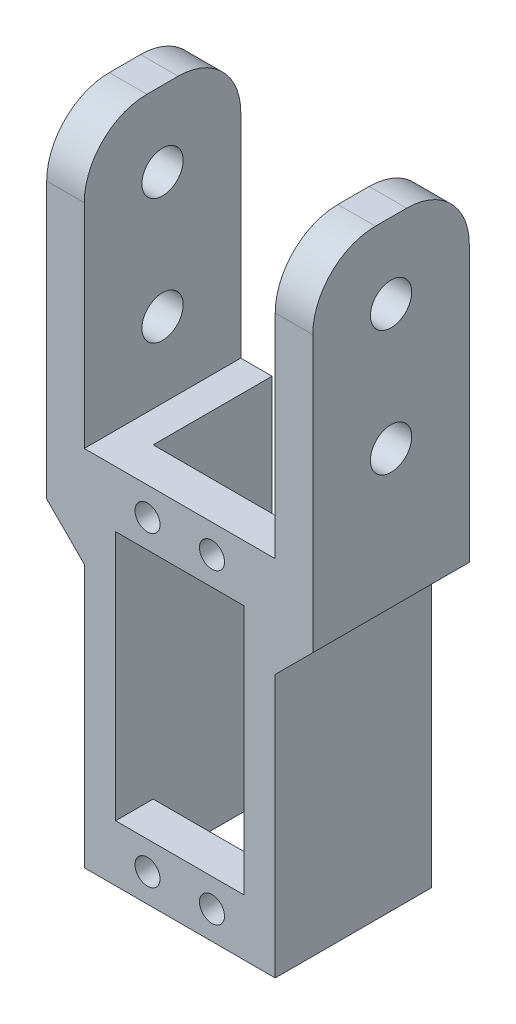
SolidWorks part; units mm, degrees
ref_plane "Front Plane" through (0, 0, 0) normal (0, 0, 1) x (1, 0, 0)
ref_plane "Top Plane" through (0, 0, 0) normal (0, 1, 0) x (1, 0, 0)
ref_plane "Right Plane" through (0, 0, 0) normal (1, 0, 0) x (0, 0, -1)
sketch "Sketch1" plane through (0, 0, 0) normal (0, 0, 1) x (1, 0, 0)
  line L1 (0, 0) -> (20.5, 0)
  line L2 (0, 0) -> (0, 9)
  line L3 (0, 9) -> (20.5, 9)
  line L4 (20.5, 0) -> (20.5, 9)
  dimension "D1" = 20.5
  dimension "D2" = 9
extrude "Boss-Extrude1" add sketch "Sketch1" along normal blind 6
sketch "Sketch2" plane through (20.5, 0, 0) normal (1, 0, 0) x (0, 0, -1)
  line L1 (-6, 9) -> (19, 9)
  line L2 (-6, 9) -> (-6, -49)
  line L3 (-6, -49) -> (19, -49)
  line L4 (19, 9) -> (19, -49)
  dimension "D1" = 25
  dimension "D2" = 58
extrude "Boss-Extrude2" add sketch "Sketch2" along normal blind 5
pattern_linear "LPattern1" count 2 spacing 49 along (0, -1, 0) of "Boss-Extrude1"
pattern_linear "LPattern2" count 2 spacing 25.5 along (-1, 0, 0) of "Boss-Extrude2"
sketch "Sketch3" plane through (0, 0, 6) normal (0, 0, 1) x (1, 0, 0)
  line L0 (0, 0) -> (20.5, 0) construction
  line L1 (25.5, 9) -> (-5, 9) construction
  circle A0 centre (5.1, 4.5) radius 2
  point P4 (10.25, 0)
  dimension "D2" = 4
  dimension "D1" = 5.15
  dimension "D3" = 4.5
extrude "Cut-Extrude1" cut sketch "Sketch3" against normal up to next
pattern_linear "LPattern3" count 2 spacing 10.3 along (1, 0, 0) count 2 spacing 49 along (0, -1, 0) of "Cut-Extrude1"
sketch "Sketch8" plane through (25.5, 0, 0) normal (1, 0, 0) x (0, 0, -1)
  line L0 (-6, 9) -> (-6, -49) construction
  line L1 (-6, 2.9974) -> (19, 2.9974)
  line L2 (-6, 2.9974) -> (-6, 52.9974)
  line L3 (-6, 52.9974) -> (19, 52.9974)
  line L4 (19, 2.9974) -> (19, 52.9974)
  line L5 (19, -49) -> (19, 9) construction
  dimension "D1" = 0
  dimension "D2" = 50
extrude "Boss-Extrude3" add sketch "Sketch8" along normal blind 6
pattern_linear "LPattern4" count 2 spacing 36.5 along (-1, 0, 0) of "Boss-Extrude3"
hole_wizard "M6 Clearance Hole1" positions "Sketch13" profile "Sketch14" hole size "M6" standard "ANSI Metric" end condition through all
sketch "Sketch13" plane through (-11, 0, 0) normal (-1, 0, 0) x (0, 0, 1)
  line L0 (-19, 2.9974) -> (-19, 52.9974) construction
  line L3 (-19, 9) -> (6, 9) construction
  line L4 (-19, 52.9974) -> (6, 52.9974) construction
  point P0 (-6.5, 21)
  dimension "D1" = 12.5
  dimension "D2" = 12
  dimension "D3" = 31.9974
sketch "Sketch14" plane through (-11, 21, -6.5) normal (0, 1, 0) x (0, 0, 1)
  line L0 (0, 0) -> (0, 42.5)
  line L1 (0, 42.5) -> (3.3, 42.5)
  line L2 (3.3, 42.5) -> (3.3, 0)
  line L5 (3.3, 0) -> (0, 0)
  line L11 (0, -6.35) -> (0, 107.95) construction
  dimension "Thru Hole Dia." = 6.6
  dimension "Thru Hole Depth" = 42.5
chamfer "Chamfer2" distance 10 angle 45 2 edges at (-5, 2.9974, -6.5) (25.5, 2.9974, -6.5)
pattern_linear "LPattern5" count 2 spacing 20 along (0, 1, 0) of "M6 Clearance Hole1"
fillet "Fillet1" radius 10 4 edges at (-8, 52.9974, 6) (28.5, 52.9974, 6) (-8, 52.9974, -19) (28.5, 52.9974, -19)
